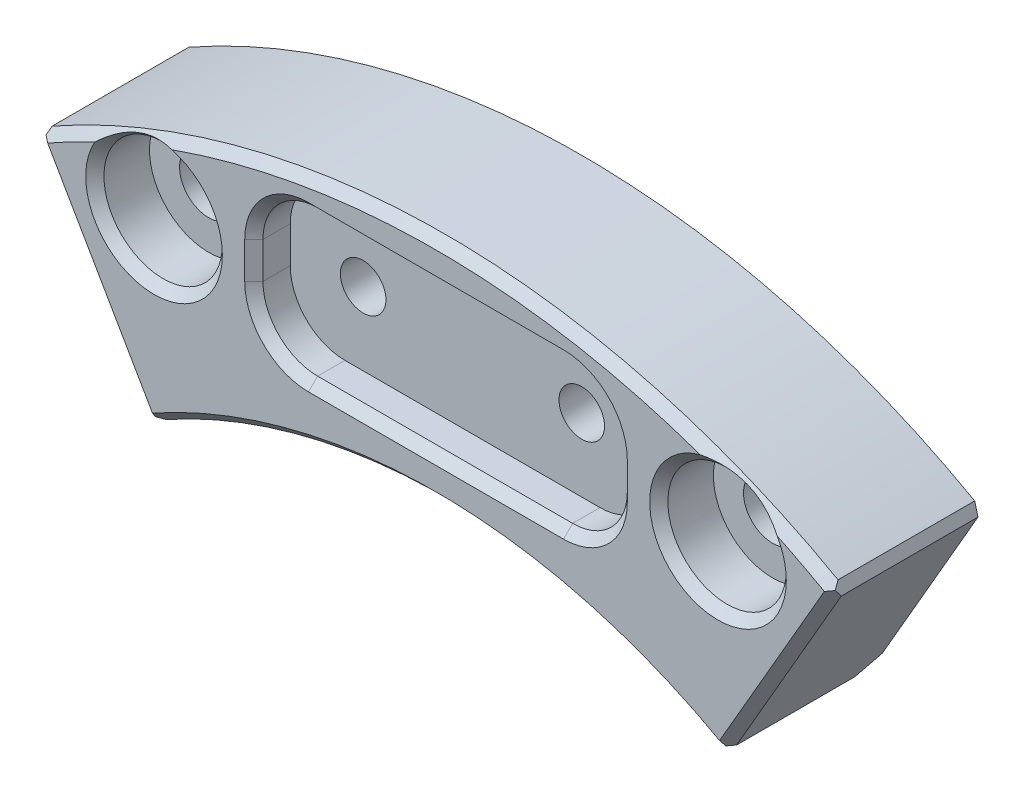
SolidWorks part; units mm, degrees
material "5052-H38"
ref_plane "Front" through (0, 0, 0) normal (0, 0, 1) x (1, 0, 0)
ref_plane "Top" through (0, 0, 0) normal (0, 1, 0) x (1, 0, 0)
ref_plane "Right" through (0, 0, 0) normal (1, 0, 0) x (0, 0, -1)
sketch "ｽｹｯﾁ2" plane through (0, 0, -16.5) normal (0, 0, 1) x (1, 0, 0)
  arc A20 (75, 25.0004) -> (86, 25.0004) centre (80.5, 25.0004) ccw construction
  arc A21 (80.5, 30.5004) -> (75, 25.0004) centre (80.5, 25.0004) ccw construction
  arc A22 (86, 25.0004) -> (80.5, 30.5004) centre (80.5, 25.0004) ccw construction
  arc A23 (102.7739, 22.2742) -> (58.2261, -22.2735) centre (80.5, 0.0004) ccw construction
  arc A24 (75, 25.0004) -> (86, 25.0004) centre (80.5, 25.0004) ccw
  arc A25 (80.5, 30.5004) -> (75, 25.0004) centre (80.5, 25.0004) ccw
  arc A26 (86, 25.0004) -> (80.5, 30.5004) centre (80.5, 25.0004) ccw
  arc A27 (102.7739, 22.2742) -> (58.2261, -22.2735) centre (80.5, 0.0004) ccw
  arc A30 (94.0977, 39.7383) -> (93.8774, 35.2962) centre (95.9987, 37.4175) ccw
  arc A31 (94.0977, 39.7383) -> (66.9023, 39.7383) centre (80.5, 0.0004) ccw
  arc A32 (67.1226, 39.5388) -> (66.9023, 39.7383) centre (65.0013, 37.4175) ccw
  arc A33 (62.88, 35.2962) -> (67.1226, 39.5388) centre (65.0013, 37.4175) ccw
  arc A34 (62.016, 37.7143) -> (62.88, 35.2962) centre (65.0013, 37.4175) ccw
  arc A35 (62.016, 37.7143) -> (42.786, 18.4843) centre (80.5, 0.0004) ccw
  arc A36 (45.2042, 17.6204) -> (42.786, 18.4843) centre (43.0829, 15.499) ccw
  arc A37 (40.9616, 13.3777) -> (45.2042, 17.6204) centre (43.0829, 15.499) ccw
  arc A38 (40.7621, 13.598) -> (40.9616, 13.3777) centre (43.0829, 15.499) ccw
  arc A39 (40.7621, 13.598) -> (40.7621, -13.5973) centre (80.5, 0.0004) ccw
  arc A40 (45.2042, -13.377) -> (40.7621, -13.5973) centre (43.0829, -15.4983) ccw
  arc A41 (42.786, -18.4836) -> (45.2042, -13.377) centre (43.0829, -15.4983) ccw
  arc A42 (42.786, -18.4836) -> (50.8015, -29.6981) centre (80.5, 0.0004) ccw
  arc A43 (50.8015, -29.6981) -> (62.016, -37.7136) centre (80.5, 0.0004) ccw
  arc A44 (67.1226, -35.2954) -> (62.016, -37.7136) centre (65.0013, -37.4168) ccw
  arc A45 (66.9023, -39.7376) -> (67.1226, -35.2954) centre (65.0013, -37.4168) ccw
  arc A46 (66.9023, -39.7376) -> (94.0977, -39.7376) centre (80.5, 0.0004) ccw
  arc A47 (93.8774, -39.5381) -> (94.0977, -39.7376) centre (95.9987, -37.4168) ccw
  arc A48 (98.12, -35.2954) -> (93.8774, -39.5381) centre (95.9987, -37.4168) ccw
  arc A49 (98.984, -37.7136) -> (98.12, -35.2954) centre (95.9987, -37.4168) ccw
  arc A50 (98.984, -37.7136) -> (118.214, -18.4836) centre (80.5, 0.0004) ccw
  arc A51 (115.7958, -17.6196) -> (118.214, -18.4836) centre (117.9171, -15.4983) ccw
  arc A52 (120.0384, -13.377) -> (115.7958, -17.6196) centre (117.9171, -15.4983) ccw
  arc A53 (120.2379, -13.5973) -> (120.0384, -13.377) centre (117.9171, -15.4983) ccw
  arc A54 (120.2379, -13.5973) -> (120.2379, 13.598) centre (80.5, 0.0004) ccw
  arc A55 (115.7958, 13.3777) -> (120.2379, 13.598) centre (117.9171, 15.499) ccw
  arc A56 (118.214, 18.4843) -> (115.7958, 13.3777) centre (117.9171, 15.499) ccw
  arc A57 (118.214, 18.4843) -> (110.1985, 29.6989) centre (80.5, 0.0004) ccw
  arc A58 (110.1985, 29.6989) -> (98.984, 37.7143) centre (80.5, 0.0004) ccw
  arc A59 (93.8774, 35.2962) -> (98.984, 37.7143) centre (95.9987, 37.4175) ccw
  arc A60 (94.0977, 39.7383) -> (93.8774, 35.2962) centre (95.9987, 37.4175) ccw
  arc A61 (94.0977, 39.7383) -> (66.9023, 39.7383) centre (80.5, 0.0004) ccw
  arc A62 (67.1226, 39.5388) -> (66.9023, 39.7383) centre (65.0013, 37.4175) ccw
  arc A63 (62.88, 35.2962) -> (67.1226, 39.5388) centre (65.0013, 37.4175) ccw
  arc A64 (62.016, 37.7143) -> (62.88, 35.2962) centre (65.0013, 37.4175) ccw
  arc A65 (62.016, 37.7143) -> (42.786, 18.4843) centre (80.5, 0.0004) ccw
  arc A66 (45.2042, 17.6204) -> (42.786, 18.4843) centre (43.0829, 15.499) ccw
  arc A67 (40.9616, 13.3777) -> (45.2042, 17.6204) centre (43.0829, 15.499) ccw
  arc A68 (40.7621, 13.598) -> (40.9616, 13.3777) centre (43.0829, 15.499) ccw
  arc A69 (40.7621, 13.598) -> (40.7621, -13.5973) centre (80.5, 0.0004) ccw
  arc A70 (45.2042, -13.377) -> (40.7621, -13.5973) centre (43.0829, -15.4983) ccw
  arc A71 (42.786, -18.4836) -> (45.2042, -13.377) centre (43.0829, -15.4983) ccw
  arc A72 (42.786, -18.4836) -> (50.8015, -29.6981) centre (80.5, 0.0004) ccw
  arc A73 (50.8015, -29.6981) -> (62.016, -37.7136) centre (80.5, 0.0004) ccw
  arc A74 (67.1226, -35.2954) -> (62.016, -37.7136) centre (65.0013, -37.4168) ccw
  arc A75 (66.9023, -39.7376) -> (67.1226, -35.2954) centre (65.0013, -37.4168) ccw
  arc A76 (66.9023, -39.7376) -> (94.0977, -39.7376) centre (80.5, 0.0004) ccw
  arc A77 (93.8774, -39.5381) -> (94.0977, -39.7376) centre (95.9987, -37.4168) ccw
  arc A78 (98.12, -35.2954) -> (93.8774, -39.5381) centre (95.9987, -37.4168) ccw
  arc A79 (98.984, -37.7136) -> (98.12, -35.2954) centre (95.9987, -37.4168) ccw
  arc A80 (98.984, -37.7136) -> (118.214, -18.4836) centre (80.5, 0.0004) ccw
  arc A81 (115.7958, -17.6196) -> (118.214, -18.4836) centre (117.9171, -15.4983) ccw
  arc A82 (120.0384, -13.377) -> (115.7958, -17.6196) centre (117.9171, -15.4983) ccw
  arc A83 (120.2379, -13.5973) -> (120.0384, -13.377) centre (117.9171, -15.4983) ccw
  arc A84 (120.2379, -13.5973) -> (120.2379, 13.598) centre (80.5, 0.0004) ccw
  arc A85 (115.7958, 13.3777) -> (120.2379, 13.598) centre (117.9171, 15.499) ccw
  arc A86 (118.214, 18.4843) -> (115.7958, 13.3777) centre (117.9171, 15.499) ccw
  arc A87 (118.214, 18.4843) -> (110.1985, 29.6989) centre (80.5, 0.0004) ccw
  arc A88 (110.1985, 29.6989) -> (98.984, 37.7143) centre (80.5, 0.0004) ccw
  arc A89 (93.8774, 35.2962) -> (98.984, 37.7143) centre (95.9987, 37.4175) ccw
  dimension "D1" = 0
sketch "ｽｹｯﾁ3" plane through (0, 0, -16.5) normal (0, 0, 1) x (1, 0, 0)
  line L0 (80.5, 0.0004) -> (58.5, 38.1055) construction
  line L1 (80.5, 0.0004) -> (102.5, 38.1055) construction
  line L2 (80.5, 0.0004) -> (80.5, 44.0004) construction
  line L3 (58.5, 38.1055) -> (64.75, 27.2802)
  line L4 (102.5, 38.1055) -> (96.25, 27.2802)
  circle A0 centre (65.0013, 37.4175) radius 1.6 construction
  circle A1 centre (95.9987, 37.4175) radius 1.6 construction
  arc A2 (64.75, 27.2802) -> (96.25, 27.2802) centre (80.5, 0.0004) cw
  arc A3 (111.6127, 31.1131) -> (49.3873, -31.1123) centre (80.5, 0.0004) ccw construction
  arc A4 (111.6127, 31.1131) -> (49.3873, -31.1123) centre (80.5, 0.0004) ccw construction
  arc A5 (105.9294, 18.5905) -> (55.0706, 18.5905) centre (80.5, 0.0004) ccw construction
  arc A6 (105.9294, 18.5905) -> (55.0706, 18.5905) centre (80.5, 0.0004) ccw construction
  arc A7 (58.5, 38.1055) -> (102.5, 38.1055) centre (80.5, 0.0004) cw construction
  arc A8 (58.5, 38.1055) -> (102.5, 38.1055) centre (80.5, 0.0004) cw
  arc A30 (94.0977, 39.7383) -> (93.8774, 35.2962) centre (95.9987, 37.4175) ccw
  arc A31 (94.0977, 39.7383) -> (66.9023, 39.7383) centre (80.5, 0.0004) ccw
  arc A32 (67.1226, 39.5388) -> (66.9023, 39.7383) centre (65.0013, 37.4175) ccw
  arc A33 (62.88, 35.2962) -> (67.1226, 39.5388) centre (65.0013, 37.4175) ccw
  arc A34 (62.016, 37.7143) -> (62.88, 35.2962) centre (65.0013, 37.4175) ccw
  arc A35 (62.016, 37.7143) -> (42.786, 18.4843) centre (80.5, 0.0004) ccw
  arc A36 (45.2042, 17.6204) -> (42.786, 18.4843) centre (43.0829, 15.499) ccw
  arc A37 (40.9616, 13.3777) -> (45.2042, 17.6204) centre (43.0829, 15.499) ccw
  arc A38 (40.7621, 13.598) -> (40.9616, 13.3777) centre (43.0829, 15.499) ccw
  arc A39 (40.7621, 13.598) -> (40.7621, -13.5973) centre (80.5, 0.0004) ccw
  arc A40 (45.2042, -13.377) -> (40.7621, -13.5973) centre (43.0829, -15.4983) ccw
  arc A41 (42.786, -18.4836) -> (45.2042, -13.377) centre (43.0829, -15.4983) ccw
  arc A42 (42.786, -18.4836) -> (50.8015, -29.6981) centre (80.5, 0.0004) ccw
  arc A43 (50.8015, -29.6981) -> (62.016, -37.7136) centre (80.5, 0.0004) ccw
  arc A44 (67.1226, -35.2954) -> (62.016, -37.7136) centre (65.0013, -37.4168) ccw
  arc A45 (66.9023, -39.7376) -> (67.1226, -35.2954) centre (65.0013, -37.4168) ccw
  arc A46 (66.9023, -39.7376) -> (94.0977, -39.7376) centre (80.5, 0.0004) ccw
  arc A47 (93.8774, -39.5381) -> (94.0977, -39.7376) centre (95.9987, -37.4168) ccw
  arc A48 (98.12, -35.2954) -> (93.8774, -39.5381) centre (95.9987, -37.4168) ccw
  arc A49 (98.984, -37.7136) -> (98.12, -35.2954) centre (95.9987, -37.4168) ccw
  arc A50 (98.984, -37.7136) -> (118.214, -18.4836) centre (80.5, 0.0004) ccw
  arc A51 (115.7958, -17.6196) -> (118.214, -18.4836) centre (117.9171, -15.4983) ccw
  arc A52 (120.0384, -13.377) -> (115.7958, -17.6196) centre (117.9171, -15.4983) ccw
  arc A53 (120.2379, -13.5973) -> (120.0384, -13.377) centre (117.9171, -15.4983) ccw
  arc A54 (120.2379, -13.5973) -> (120.2379, 13.598) centre (80.5, 0.0004) ccw
  arc A55 (115.7958, 13.3777) -> (120.2379, 13.598) centre (117.9171, 15.499) ccw
  arc A56 (118.214, 18.4843) -> (115.7958, 13.3777) centre (117.9171, 15.499) ccw
  arc A57 (118.214, 18.4843) -> (110.1985, 29.6989) centre (80.5, 0.0004) ccw
  arc A58 (110.1985, 29.6989) -> (98.984, 37.7143) centre (80.5, 0.0004) ccw
  arc A59 (93.8774, 35.2962) -> (98.984, 37.7143) centre (95.9987, 37.4175) ccw
  arc A60 (94.0977, 39.7383) -> (93.8774, 35.2962) centre (95.9987, 37.4175) ccw construction
  arc A61 (94.0977, 39.7383) -> (66.9023, 39.7383) centre (80.5, 0.0004) ccw construction
  arc A62 (67.1226, 39.5388) -> (66.9023, 39.7383) centre (65.0013, 37.4175) ccw construction
  arc A63 (62.88, 35.2962) -> (67.1226, 39.5388) centre (65.0013, 37.4175) ccw construction
  arc A64 (62.016, 37.7143) -> (62.88, 35.2962) centre (65.0013, 37.4175) ccw construction
  arc A65 (62.016, 37.7143) -> (42.786, 18.4843) centre (80.5, 0.0004) ccw construction
  arc A66 (45.2042, 17.6204) -> (42.786, 18.4843) centre (43.0829, 15.499) ccw construction
  arc A67 (40.9616, 13.3777) -> (45.2042, 17.6204) centre (43.0829, 15.499) ccw construction
  arc A68 (40.7621, 13.598) -> (40.9616, 13.3777) centre (43.0829, 15.499) ccw construction
  arc A69 (40.7621, 13.598) -> (40.7621, -13.5973) centre (80.5, 0.0004) ccw construction
  arc A70 (45.2042, -13.377) -> (40.7621, -13.5973) centre (43.0829, -15.4983) ccw construction
  arc A71 (42.786, -18.4836) -> (45.2042, -13.377) centre (43.0829, -15.4983) ccw construction
  arc A72 (42.786, -18.4836) -> (50.8015, -29.6981) centre (80.5, 0.0004) ccw construction
  arc A73 (50.8015, -29.6981) -> (62.016, -37.7136) centre (80.5, 0.0004) ccw construction
  arc A74 (67.1226, -35.2954) -> (62.016, -37.7136) centre (65.0013, -37.4168) ccw construction
  arc A75 (66.9023, -39.7376) -> (67.1226, -35.2954) centre (65.0013, -37.4168) ccw construction
  arc A76 (66.9023, -39.7376) -> (94.0977, -39.7376) centre (80.5, 0.0004) ccw construction
  arc A77 (93.8774, -39.5381) -> (94.0977, -39.7376) centre (95.9987, -37.4168) ccw construction
  arc A78 (98.12, -35.2954) -> (93.8774, -39.5381) centre (95.9987, -37.4168) ccw construction
  arc A79 (98.984, -37.7136) -> (98.12, -35.2954) centre (95.9987, -37.4168) ccw construction
  arc A80 (98.984, -37.7136) -> (118.214, -18.4836) centre (80.5, 0.0004) ccw construction
  arc A81 (115.7958, -17.6196) -> (118.214, -18.4836) centre (117.9171, -15.4983) ccw construction
  arc A82 (120.0384, -13.377) -> (115.7958, -17.6196) centre (117.9171, -15.4983) ccw construction
  arc A83 (120.2379, -13.5973) -> (120.0384, -13.377) centre (117.9171, -15.4983) ccw construction
  arc A84 (120.2379, -13.5973) -> (120.2379, 13.598) centre (80.5, 0.0004) ccw construction
  arc A85 (115.7958, 13.3777) -> (120.2379, 13.598) centre (117.9171, 15.499) ccw construction
  arc A86 (118.214, 18.4843) -> (115.7958, 13.3777) centre (117.9171, 15.499) ccw construction
  arc A87 (118.214, 18.4843) -> (110.1985, 29.6989) centre (80.5, 0.0004) ccw construction
  arc A88 (110.1985, 29.6989) -> (98.984, 37.7143) centre (80.5, 0.0004) ccw construction
  arc A89 (93.8774, 35.2962) -> (98.984, 37.7143) centre (95.9987, 37.4175) ccw construction
  dimension "D2" = 3.2
  dimension "D3" = 30
  dimension "D4" = 30
  dimension "D1" = 0
extrude "ﾎﾞｽ - 押し出し1" add sketch "ｽｹｯﾁ3" along normal blind 8 contours L3 A2 L4 | L4 L3 | A8 L3 L4 A1 A0 region at (80.5, 43.5501, -16.5) region at (80.5, 35.1314, -16.5)
chamfer "面取り7" distance 1.5 angle 45 1 edges at (80.5, 31.5004, -16.5)
hole_wizard "M3 穴付きねじ用座ぐり穴1" positions "ｽｹｯﾁ12" profile "ｽｹｯﾁ13" counterbore size "M3" standard "JIS" end condition up to next
sketch "ｽｹｯﾁ12" plane through (0, 0, -8.5) normal (0, 0, 1) x (1, 0, 0)
  point P0 (65.0229, 37.391)
  point P2 (95.9771, 37.391)
sketch "ｽｹｯﾁ13" plane through (65.0229, 37.391, -8.5) normal (1, 0, 0) x (0, -1, 0)
  line L0 (0, 0) -> (0, 8)
  line L1 (0, 8) -> (1.6, 8)
  line L3 (1.6, 8) -> (1.6, 3)
  line L4 (1.6, 3) -> (3.25, 3)
  line L5 (3.25, 3) -> (3.25, 0)
  line L7 (3.25, 0) -> (0, 0)
  line L11 (0, -6.35) -> (0, 107.95) construction
  dimension "通し穴の直径" = 3.2
  dimension "通し穴の深さ" = 8
  dimension "座ぐり穴の直径" = 6.5
  dimension "座ぐり穴の深さ" = 3
sketch "ｽｹｯﾁ14" plane through (0, 0, -8.5) normal (0, 0, 1) x (1, 0, 0)
  line L0 (80.5, 44.0004) -> (80.5, 31.5004) construction
  line L1 (70.5, 37.7504) -> (90.5, 37.7504) construction
  line L2 (70.5, 33.7504) -> (90.5, 33.7504)
  line L3 (70.5, 33.7504) -> (70.5, 41.7504)
  line L4 (70.5, 41.7504) -> (90.5, 41.7504)
  line L5 (90.5, 33.7504) -> (90.5, 41.7504)
  line L6 (70.5, 33.7504) -> (90.5, 41.7504) construction
  line L7 (70.5, 41.7504) -> (90.5, 33.7504) construction
  arc A0 (102.5, 38.1055) -> (58.5, 38.1055) centre (80.5, 0.0004) ccw construction
  arc A1 (96.25, 27.2802) -> (64.75, 27.2802) centre (80.5, 0.0004) ccw construction
  circle A2 centre (74.5, 37.7504) radius 1.5
  circle A4 centre (86.5, 37.7504) radius 1.5
  point P8 (80.5, 37.7504)
  dimension "D3" = 3
  dimension "D4" = 6
  dimension "D1" = 8
  dimension "D2" = 20
sketch "ｽｹｯﾁ17" plane through (0, 0, -8.5) normal (0, 0, 1) x (1, 0, 0)
  line L1 (73.5, 41.7504) -> (87.5, 41.7504)
  line L2 (70.5, 38.7504) -> (70.5, 36.7504)
  line L3 (73.5, 33.7504) -> (87.5, 33.7504)
  line L4 (90.5, 38.7504) -> (90.5, 36.7504)
  line L5 (70.5, 41.7504) -> (90.5, 33.7504) construction
  line L6 (70.5, 33.7504) -> (90.5, 41.7504) construction
  arc A0 (90.5, 38.7504) -> (87.5, 41.7504) centre (87.5, 38.7504) ccw
  arc A1 (87.5, 33.7504) -> (90.5, 36.7504) centre (87.5, 36.7504) ccw
  arc A2 (70.5, 36.7504) -> (73.5, 33.7504) centre (73.5, 36.7504) ccw
  arc A3 (73.5, 41.7504) -> (70.5, 38.7504) centre (73.5, 38.7504) ccw
  point P4 (80.5, 37.7504)
  dimension "D1" = 3
extrude "ｶｯﾄ - 押し出し6" cut sketch "ｽｹｯﾁ17" against normal blind 2
chamfer "面取り8" distance 0.5 angle 45 14 edges at (80.5, 44.0004, -8.5) (99.375, 32.6928, -8.5) (80.5, 31.5004, -8.5) (61.625, 32.6928, -8.5) (99.2271, 37.391, -8.5) (68.2729, 37.391, -8.5) (80.5, 41.7504, -8.5) (71.3787, 40.8717, -8.5) (70.5, 37.7504, -8.5) (71.3787, 34.629, -8.5) (80.5, 33.7504, -8.5) (89.6213, 34.629, -8.5) (90.5, 37.7504, -8.5) (89.6213, 40.8717, -8.5)
chamfer "面取り9" distance 0.5 angle 45 4 edges at (96.25, 27.2802, -12) (64.75, 27.2802, -12) (58.5, 38.1055, -12.75) (102.5, 38.1055, -12.75)
hole_wizard "M3x0.5 ねじ穴1" positions "ｽｹｯﾁ19" profile "ｽｹｯﾁ20" tap size "M3x0.5" standard "JIS"
sketch "ｽｹｯﾁ19" plane through (0, 0, -10.5) normal (0, 0, 1) x (1, 0, 0)
  point P0 (74.5, 37.7504)
  point P3 (86.5, 37.7504)
sketch "ｽｹｯﾁ20" plane through (74.5, 37.7504, -10.5) normal (1, 0, 0) x (0, -1, 0)
  line L0 (0, 0) -> (0, 9.2511)
  line L1 (0, 9.2511) -> (1.25, 8.5)
  line L2 (1.25, 8.5) -> (1.25, 0)
  line L5 (1.25, 0) -> (0, 0)
  line L10 (0, 9.2511) -> (-1.25, 8.5) construction
  line L11 (0, -6.35) -> (0, 107.95) construction
  dimension "ねじ下穴ﾄﾞﾘﾙ直径" = 2.5
  dimension "ねじ下穴ﾄﾞﾘﾙの深さ" = 8.5
  dimension "ﾄﾞﾘﾙ角度" = 118
